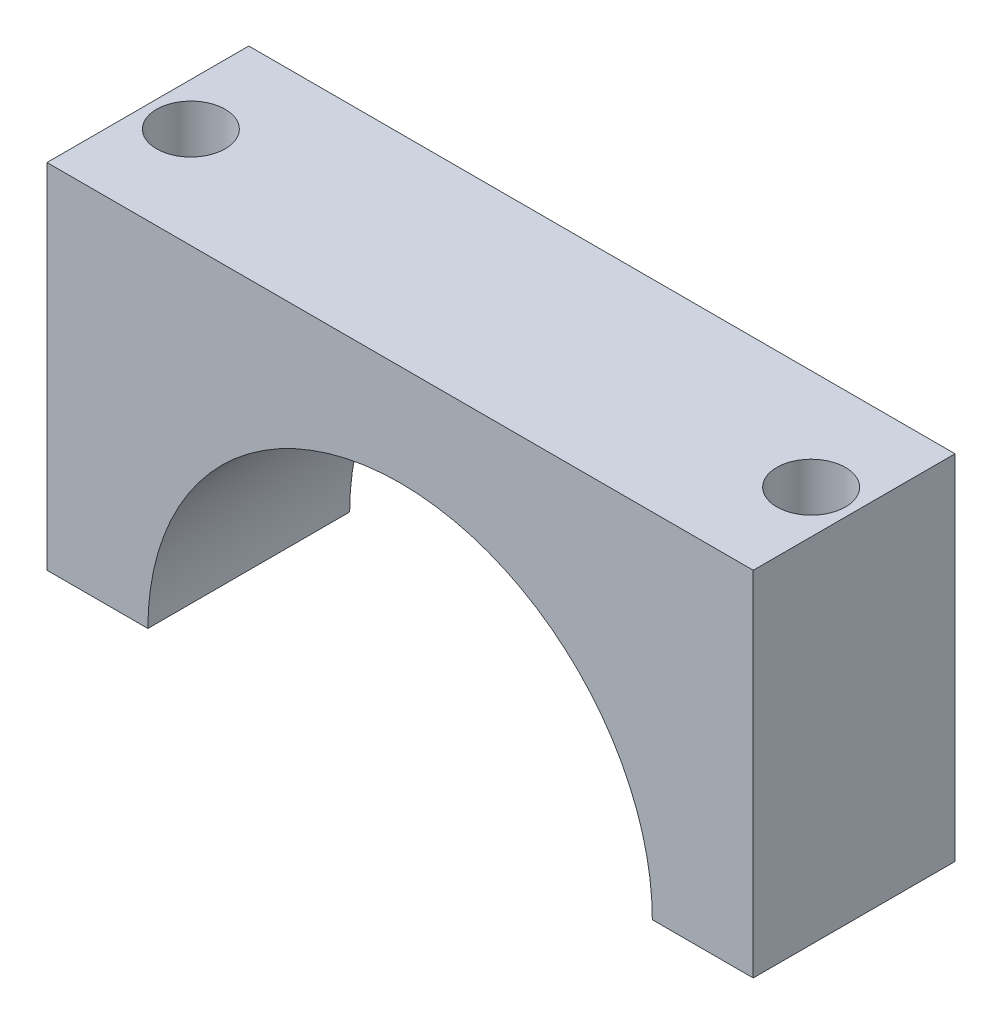
SolidWorks part; units mm, degrees
material "6061 Alloy"
ref_plane "Front Plane" through (0, 0, 0) normal (0, 0, 1) x (1, 0, 0)
ref_plane "Top Plane" through (0, 0, 0) normal (0, 1, 0) x (1, 0, 0)
ref_plane "Right Plane" through (0, 0, 0) normal (1, 0, 0) x (0, 0, -1)
sketch "Sketch2" plane through (0, 0, 0) normal (0, 0, 1) x (1, 0, 0)
  line L0 (12.5, 0) -> (17.5, 0)
  line L2 (-17.5, 0) -> (-17.5, 17.5)
  line L3 (-17.5, 17.5) -> (17.5, 17.5)
  line L4 (17.5, 0) -> (17.5, 17.5)
  line L7 (-12.5, 0) -> (-17.5, 0)
  arc A0 (12.5, 0) -> (-12.5, 0) centre (0, 0) ccw
  dimension "D1" = 12.5
  dimension "D2" = 17.5
  dimension "D3" = 35
  dimension "D4" = 17.5
extrude "Boss-Extrude1" add sketch "Sketch2" along normal blind 10
hole_wizard "M3 Clearance Hole1" positions "Sketch5" profile "Sketch4" hole size "M3" standard "ANSI Metric" end condition through all
sketch "Sketch5" plane through (0, 17.5, 0) normal (0, 1, 0) x (1, 0, 0)
  line L1 (17.5, -10) -> (-17.5, -10) construction
  line L7 (0, 0) -> (0, -10) construction
  line L8 (17.5, 0) -> (-17.5, 0) construction
  point P0 (-15.37, -5)
  point P2 (15.37, -5)
  point P29 (-23.4147, -5)
  point P30 (-20.8652, -5)
  point P31 (13.265, -5)
  point P34 (0, 0)
  point P35 (-15.0081, -5)
  dimension "D1" = 15.37
  dimension "D2" = 5
  dimension "D3" = 5
  dimension "D4" = 30.74
sketch "Sketch4" plane through (-15.37, 17.5, 5) normal (1, 0, 0) x (0, 0, 1)
  line L0 (0, 0) -> (0, 17.5)
  line L1 (0, 17.5) -> (1.7, 17.5)
  line L2 (1.7, 17.5) -> (1.7, 0)
  line L5 (1.7, 0) -> (0, 0)
  line L11 (0, -6.35) -> (0, 107.95) construction
  dimension "Thru Hole Dia." = 3.4
  dimension "Thru Hole Depth" = 17.5
